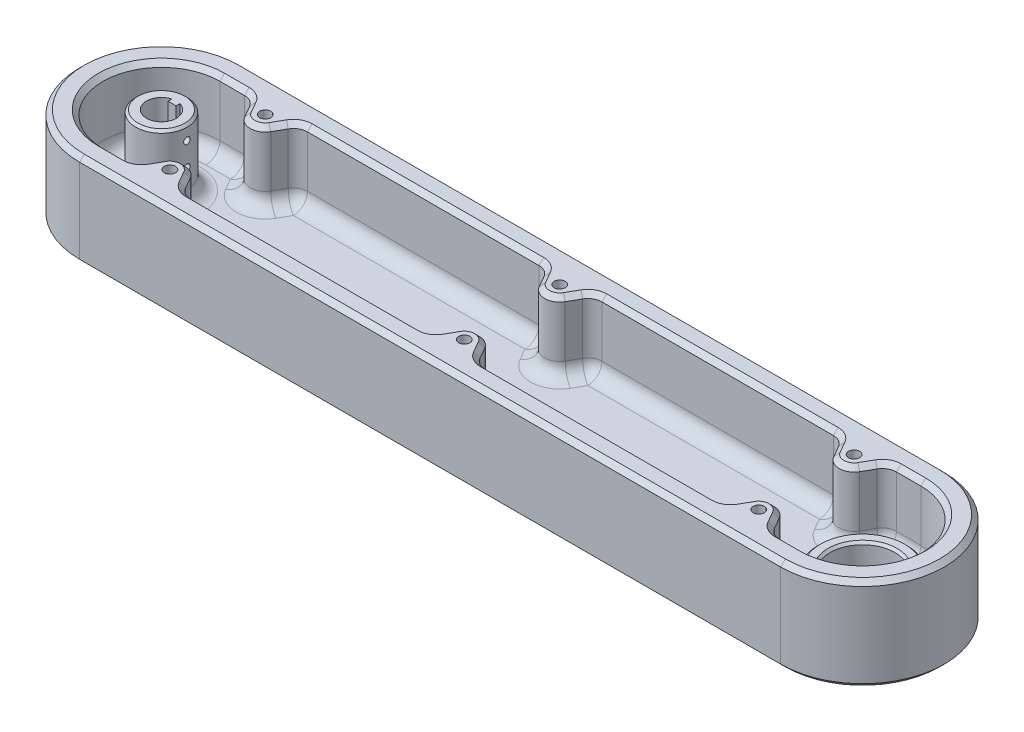
SolidWorks part; units mm, degrees
ref_plane "Front Plane" through (0, 0, 0) normal (0, 0, 1) x (1, 0, 0)
ref_plane "Top Plane" through (0, 0, 0) normal (0, 1, 0) x (1, 0, 0)
ref_plane "Right Plane" through (0, 0, 0) normal (1, 0, 0) x (0, 0, -1)
sketch "Sketch1" plane through (0, 0, 0) normal (0, 1, 0) x (1, 0, 0)
  line L0 (-95.25, 0) -> (95.25, 0) construction
  line L1 (0, -55.9739) -> (0, 55.9739) construction
  line L2 (-95.25, 22.225) -> (95.25, 22.225)
  line L3 (-95.25, -22.225) -> (95.25, -22.225)
  arc A0 (-95.25, 22.225) -> (-95.25, -22.225) centre (-95.25, 0) ccw
  arc A1 (95.25, 22.225) -> (95.25, -22.225) centre (95.25, 0) cw
  point P4 (0, 0)
  point P10 (0, 0)
  dimension "D2" = 44.45
  dimension "D1" = 190.5
extrude "MainBlock" add sketch "Sketch1" along normal blind 25.4
sketch "Sketch2" plane through (0, 25.4, 0) normal (0, 1, 0) x (1, 0, 0)
  line L0 (0, 0) -> (155.7407, 0) construction
  line L1 (0, 0) -> (0, 57.4416) construction
  line L2 (-95.25, -22.225) -> (95.25, -22.225) construction
  line L3 (95.25, 22.225) -> (-95.25, 22.225) construction
  line L4 (-95.25, -22.225) -> (95.25, -22.225) construction
  line L5 (95.25, 22.225) -> (-95.25, 22.225) construction
  line L6 (-95.25, 15.875) -> (95.25, 15.875)
  line L7 (-95.25, -15.875) -> (95.25, -15.875)
  arc A0 (95.25, -22.225) -> (95.25, 22.225) centre (95.25, 0) ccw construction
  arc A1 (-95.25, 22.225) -> (-95.25, -22.225) centre (-95.25, 0) ccw construction
  arc A2 (95.25, -22.225) -> (95.25, 22.225) centre (95.25, 0) ccw construction
  arc A3 (-95.25, 22.225) -> (-95.25, -22.225) centre (-95.25, 0) ccw construction
  arc A4 (-95.25, 15.875) -> (-95.25, -15.875) centre (-95.25, 0) ccw
  arc A5 (95.25, 15.875) -> (95.25, -15.875) centre (95.25, 0) cw
  point P18 (0, 15.875)
  point P19 (0, -15.875)
  dimension "D1" = 6.35
extrude "MainPocket" cut sketch "Sketch2" against normal blind 19.05
sketch "Sketch3" plane through (0, 6.35, 0) normal (0, 1, 0) x (1, 0, 0)
  line L0 (0, 0) -> (50000, 0) construction
  line L1 (0, 0) -> (0, 50000) construction
  line L2 (-95.25, 0) -> (-95.25, 50000) construction
  line L3 (-96.3295, 3.918) -> (-96.3295, 2.8734)
  line L4 (-96.3295, 2.8734) -> (-94.1705, 2.8734)
  line L5 (-1111.1599, 4.064) -> (-100.931, 4.064) construction
  line L6 (-94.1705, 3.918) -> (-94.1705, 2.8734)
  line L7 (-89.569, 4.064) -> (49904.75, 4.064) construction
  arc A0 (95.25, -15.875) -> (95.25, 15.875) centre (95.25, 0) ccw construction
  arc A1 (-95.25, 15.875) -> (-95.25, -15.875) centre (-95.25, 0) ccw construction
  arc A2 (95.25, -15.875) -> (95.25, 15.875) centre (95.25, 0) ccw construction
  arc A3 (-95.25, 15.875) -> (-95.25, -15.875) centre (-95.25, 0) ccw construction
  arc A4 (-96.3295, 3.918) -> (-94.1705, 3.918) centre (-95.25, 0) ccw
  circle A5 centre (-95.25, 0) radius 6.985
  point P22 (-95.25, 2.8734)
  point P28 (95.25, 2.8734)
  dimension "D1" = 8.128
  dimension "D2" = 13.97
  dimension "D3" = 2.159
  dimension "D4" = 1.1906
extrude "ShaftKey" add sketch "Sketch3" along normal up to surface (19.05 mm away) up to face at (0, 25.4, 0)
sketch "Sketch4" plane through (0, 6.35, 0) normal (0, 1, 0) x (1, 0, 0)
  line L3 (-94.1705, 2.8734) -> (-96.3295, 2.8734)
  line L4 (-96.3295, 2.8734) -> (-96.3295, 3.918)
  line L5 (-94.1705, 3.918) -> (-94.1705, 2.8734)
  line L6 (-94.1705, 2.8734) -> (-96.3295, 2.8734)
  line L7 (-96.3295, 2.8734) -> (-96.3295, 3.918)
  line L8 (-94.1705, 3.918) -> (-94.1705, 2.8734)
  arc A1 (-96.3295, 3.918) -> (-94.1705, 3.918) centre (-95.25, 0) ccw
  arc A2 (-96.3295, 3.918) -> (-94.1705, 3.918) centre (-95.25, 0) ccw
  arc A4 (95.25, -15.875) -> (95.25, 15.875) centre (95.25, 0) ccw construction
  arc A5 (95.25, -15.875) -> (95.25, 15.875) centre (95.25, 0) ccw construction
  circle A6 centre (95.25, 0) radius 3.81
  dimension "D2" = 7.62
  dimension "D1" = 0
extrude "ShaftHole" cut sketch "Sketch4" against normal up to surface (6.35 mm away) up to face at (0, 0, 0)
sketch "Sketch5" plane through (0, 6.35, 0) normal (0, 1, 0) x (1, 0, 0)
  line L0 (0, 1.6141) -> (0, 58.9249) construction
  line L1 (0, 0) -> (50000, 0) construction
  line L2 (-95.25, 1.3136) -> (-95.25, 50001.3136) construction
  line L3 (95.25, 15.875) -> (-95.25, 15.875) construction
  line L6 (-83.5385, 10.9376) -> (-86.36, 15.875)
  line L7 (-76.4815, 10.9376) -> (-73.66, 15.875)
  line L8 (-73.66, 15.875) -> (-86.36, 15.875)
  line L9 (-3.5285, 10.9376) -> (-6.35, 15.875)
  line L10 (3.5285, 10.9376) -> (6.35, 15.875)
  line L11 (-6.35, 15.875) -> (6.35, 15.875)
  line L12 (-6.35, -15.875) -> (6.35, -15.875)
  line L13 (3.5285, -10.9376) -> (6.35, -15.875)
  line L14 (-3.5285, -10.9376) -> (-6.35, -15.875)
  line L26 (95.25, 15.875) -> (-95.25, 15.875) construction
  line L27 (-73.66, -15.875) -> (-86.36, -15.875)
  line L28 (-76.4815, -10.9376) -> (-73.66, -15.875)
  line L29 (-83.5385, -10.9376) -> (-86.36, -15.875)
  line L30 (83.5385, -10.9376) -> (86.36, -15.875)
  line L31 (76.4815, -10.9376) -> (73.66, -15.875)
  line L32 (73.66, -15.875) -> (86.36, -15.875)
  line L33 (73.66, 15.875) -> (86.36, 15.875)
  line L34 (76.4815, 10.9376) -> (73.66, 15.875)
  line L35 (83.5385, 10.9376) -> (86.36, 15.875)
  circle A0 centre (-95.25, 0) radius 6.985 construction
  circle A1 centre (-95.25, 0) radius 6.985 construction
  circle A2 centre (-80.01, 12.954) radius 1.524
  arc A3 (-83.5385, 10.9376) -> (-76.4815, 10.9376) centre (-80.01, 12.954) ccw
  circle A6 centre (0, 12.954) radius 1.524
  arc A7 (-3.5285, 10.9376) -> (3.5285, 10.9376) centre (0, 12.954) ccw
  arc A8 (-3.5285, -10.9376) -> (3.5285, -10.9376) centre (0, -12.954) cw
  circle A9 centre (0, -12.954) radius 1.524
  arc A21 (-83.5385, -10.9376) -> (-76.4815, -10.9376) centre (-80.01, -12.954) cw
  circle A22 centre (-80.01, -12.954) radius 1.524
  circle A23 centre (80.01, -12.954) radius 1.524
  arc A24 (83.5385, -10.9376) -> (76.4815, -10.9376) centre (80.01, -12.954) ccw
  arc A25 (83.5385, 10.9376) -> (76.4815, 10.9376) centre (80.01, 12.954) cw
  circle A26 centre (80.01, 12.954) radius 1.524
  point P2 (-85.2392, -15.875)
  point P6 (0, 0)
  point P33 (-79.3076, 12.954)
  point P39 (-71.9675, 15.875)
  point P58 (-78.7063, 12.954)
  dimension "D1" = 3.048
  dimension "D6" = 3.048
  dimension "D2" = 4.064
  dimension "D7" = 2.54
  dimension "D8" = 12.954
  dimension "D3" = 12.954
  dimension "D5" = 12.7
  dimension "D4" = 15.24
  dimension "D9" = 12.7
extrude "ThreadedInsertSupports" add sketch "Sketch5" along a picked direction on the side of the normal up to surface (19.05 mm away)
sketch "Sketch8" plane through (0, 0, 0) normal (0, -1, 0) x (1, 0, 0)
  line L0 (-96.3295, -3.918) -> (-96.3295, -2.8734) construction
  line L1 (-94.1705, -2.8734) -> (-94.1705, -3.918) construction
  line L2 (-96.3295, -2.8734) -> (-94.1705, -2.8734) construction
  line L3 (-96.3295, -3.918) -> (-96.3295, -2.8734)
  line L4 (-94.1705, -2.8734) -> (-94.1705, -3.918)
  line L5 (-96.3295, -2.8734) -> (-94.1705, -2.8734)
  line L6 (0, 0) -> (0, 50000) construction
  circle A0 centre (-95.25, 0) radius 6.35
  arc A1 (-94.1705, -3.918) -> (-96.3295, -3.918) centre (-95.25, 0) ccw construction
  arc A2 (-94.1705, -3.918) -> (-96.3295, -3.918) centre (-95.25, 0) ccw
  circle A5 centre (95.25, 0) radius 3.81 construction
  circle A6 centre (95.25, 0) radius 3.81 construction
  circle A7 centre (95.25, 0) radius 6.35 construction
  dimension "D1" = 12.7
  dimension "D2" = 12.7
extrude "BearingSpacer" add sketch "Sketch8" along a picked direction on the side of the normal blind 6.35
fillet "Fillet3" radius 2.54 1 edges at (-95.25, 0, 6.35)
ref_plane "keyPlane1" through (-95.25, 0, 0) normal (-1, 0, 0) x (0, 0, 1)
sketch "Sketch10" plane through (0, 6.35, 0) normal (0, 1, 0) x (1, 0, 0)
  circle A2 centre (95.25, 0) radius 12.065
  circle A3 centre (95.25, 0) radius 8.763
  dimension "D1" = 24.13
  dimension "D2" = 17.526
extrude "Boss-Extrude1" add sketch "Sketch10" along normal blind 6.35
sketch "Sketch7" plane through (0, 0, 0) normal (1, 0, 0) x (0, 0, -1)
  line L0 (6.985, 25.4) -> (-6.985, 25.4) construction
  line L1 (6.985, 6.35) -> (-6.985, 6.35) construction
  line L2 (6.985, 25.4) -> (-6.985, 25.4) construction
  line L3 (6.985, 6.35) -> (-6.985, 6.35) construction
  line L4 (0, 0) -> (0, 50000) construction
  line L5 (-22.225, 0) -> (22.225, 0) construction
  circle A0 centre (0, 21.59) radius 0.889
  circle A1 centre (0, 15.24) radius 0.889
  point P8 (0, 0)
  dimension "D1" = 1.778
  dimension "D2" = 1.778
  dimension "D3" = 3.81
  dimension "D4" = 10.16
extrude "Cut-Extrude4" cut sketch "Sketch7" against normal mid plane 190.5
fillet "Fillet4" radius 3.81 42 edges at (-95.25, 6.35, -6.985) (80.01, 6.35, -8.89) (84.9492, 6.35, -13.4063) (90.805, 6.35, -15.875) (111.125, 6.35, 0) (90.805, 6.35, 15.875) (84.9492, 6.35, 13.4063) (80.01, 6.35, 8.89) (75.0708, 6.35, 13.4063) (40.005, 6.35, 15.875) (4.9392, 6.35, 13.4063) (0, 6.35, 8.89) (-4.9392, 6.35, 13.4063) (-40.005, 6.35, 15.875) (-75.0708, 6.35, 13.4063) (-80.01, 6.35, 8.89) (-84.9492, 6.35, 13.4063) (-90.805, 6.35, 15.875) (-111.125, 6.35, 0) (-90.805, 6.35, -15.875) (-84.9492, 6.35, -13.4063) (-80.01, 6.35, -8.89) (-75.0708, 6.35, -13.4063) (-40.005, 6.35, -15.875) (-4.9392, 6.35, -13.4063) (0, 6.35, -8.89) (4.9392, 6.35, -13.4063) (40.005, 6.35, -15.875) (75.0708, 6.35, -13.4063) (95.25, 6.35, -12.065) (86.36, 15.875, 15.875) (73.66, 15.875, 15.875) (6.35, 15.875, 15.875) (-6.35, 15.875, 15.875) (-73.66, 15.875, 15.875) (-86.36, 15.875, 15.875) (86.36, 15.875, -15.875) (73.66, 15.875, -15.875) (6.35, 15.875, -15.875) (-6.35, 15.875, -15.875) (-73.66, 15.875, -15.875) (-86.36, 15.875, -15.875)
chamfer "Chamfer1" distance 0.635 angle 45 3 edges at (95.25, 12.7, 8.763) (95.25, 12.7, 12.065) (-95.25, 25.4, 6.985)
chamfer "Chamfer2" distance 1.27 angle 45 48 edges at (0, 0, 22.225) (117.475, 0, 0) (-117.475, 0, 0) (0, 0, -22.225) (40.005, 25.4, 15.875) (73.3613, 25.4, 15.3603) (6.6487, 25.4, 15.3603) (75.6192, 25.4, 12.4465) (4.3908, 25.4, 12.4465) (80.01, 25.4, 8.89) (0, 25.4, 8.89) (84.4008, 25.4, 12.4465) (-4.3908, 25.4, 12.4465) (86.6587, 25.4, 15.3603) (-6.6487, 25.4, 15.3603) (91.9105, 25.4, 15.875) (-40.005, 25.4, 15.875) (111.125, 25.4, 0) (-73.3613, 25.4, 15.3603) (91.9105, 25.4, -15.875) (-75.6192, 25.4, 12.4465) (86.6587, 25.4, -15.3603) (-80.01, 25.4, 8.89) (84.4008, 25.4, -12.4465) (-84.4008, 25.4, 12.4465) (80.01, 25.4, -8.89) (-86.6587, 25.4, 15.3603) (75.6192, 25.4, -12.4465) (-91.9105, 25.4, 15.875) (73.3613, 25.4, -15.3603) (-111.125, 25.4, 0) (40.005, 25.4, -15.875) (-91.9105, 25.4, -15.875) (6.6487, 25.4, -15.3603) (-86.6587, 25.4, -15.3603) (4.3908, 25.4, -12.4465) (-84.4008, 25.4, -12.4465) (0, 25.4, -8.89) (-80.01, 25.4, -8.89) (-4.3908, 25.4, -12.4465) (-75.6192, 25.4, -12.4465) (-6.6487, 25.4, -15.3603) (-73.3613, 25.4, -15.3603) (-40.005, 25.4, -15.875) (0, 25.4, 22.225) (117.475, 25.4, 0) (-117.475, 25.4, 0) (0, 25.4, -22.225)
chamfer "Chamfer3" distance 0.635 angle 45 1 edges at (-95.25, -6.35, -6.35)
equation "\"D3@Sketch5\"=\"D8@Sketch5\""
